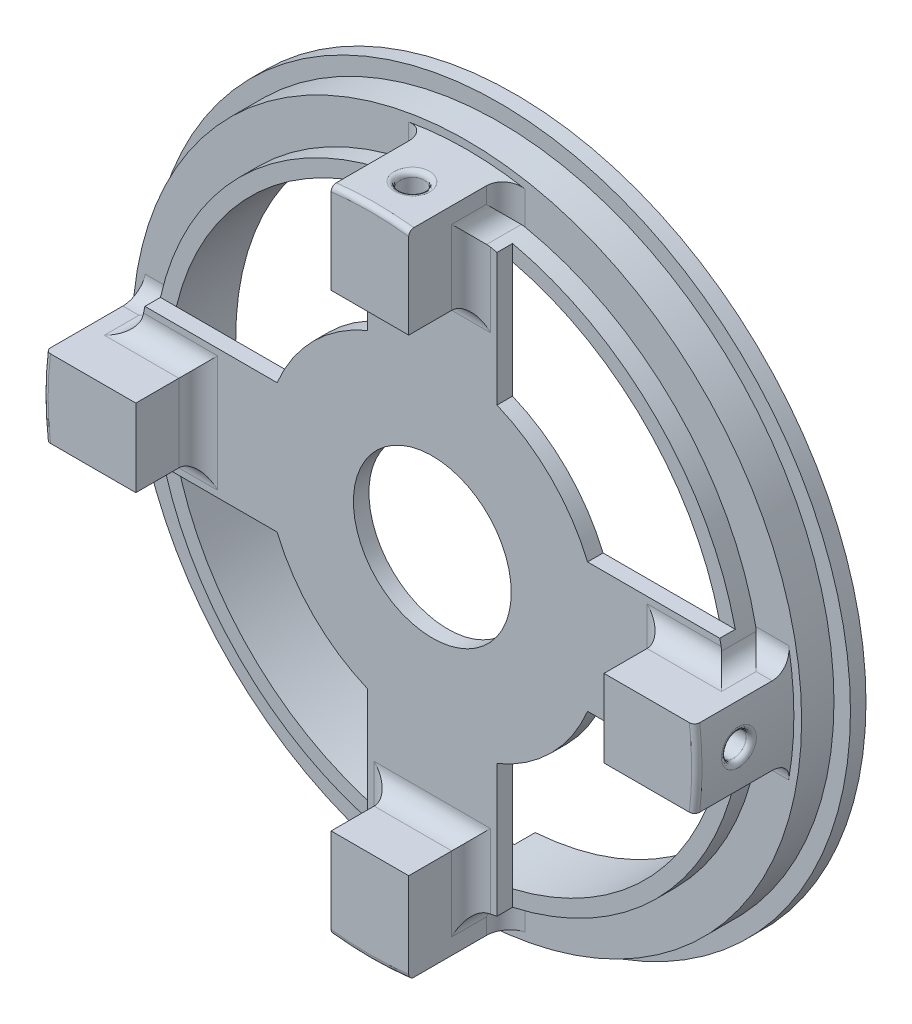
SolidWorks part; units mm, degrees
ref_plane "Front Plane" through (0, 0, 0) normal (0, 0, 1) x (1, 0, 0)
ref_plane "Top Plane" through (0, 0, 0) normal (0, 1, 0) x (1, 0, 0)
ref_plane "Right Plane" through (0, 0, 0) normal (1, 0, 0) x (0, 0, -1)
sketch "Sketch1" plane through (0, 0, 0) normal (0, 0, 1) x (1, 0, 0)
  circle A0 centre (0, 0) radius 54.3 construction
  circle A1 centre (0, 0) radius 54.3
  circle A4 centre (0, 0) radius 43.15
  circle A5 centre (0, 0) radius 43.15
extrude "Boss-Extrude1" add sketch "Sketch1" along normal blind 2.4
sketch "Sketch6" plane through (0, 0, 10.2) normal (0, 0, 1) x (1, 0, 0)
  circle A2 centre (0, 0) radius 43.15 construction
  circle A3 centre (0, 0) radius 43.15
extrude "Boss-Extrude4" add sketch "Sketch6" along normal blind 2.4 from offset 0.15 separate body
sketch "Sketch7" plane through (0, 0, 2.4) normal (0, 0, 1) x (1, 0, 0)
  circle A0 centre (0, 0) radius 43.15 construction
  circle A1 centre (0, 0) radius 43.15
extrude "Extrude-Thin2" add sketch "Sketch7" along normal up to surface (10.35 mm away) thin up to face at (43.15, 0, 12.75) thin type one direction wall 2.4
sketch "Sketch9" plane through (0, 0, 12.75) normal (0, 0, 1) x (1, 0, 0)
  circle A2 centre (0, 0) radius 12.2
  circle A3 centre (0, 0) radius 12.2
  dimension "D1" = 0.2
extrude "Cut-Extrude1" cut sketch "Sketch9" against normal up to surface (2.4 mm away) up to face at (43.15, 0, 10.35)
sketch "Sketch10" plane through (0, 0, 12.75) normal (0, 0, 1) x (1, 0, 0)
  line L0 (0, -45.55) -> (0, 45.55) construction
  line L1 (45.55, 0) -> (-45.55, 0) construction
  line L2 (10, -44.4387) -> (10, 44.4387)
  line L3 (44.4387, -10) -> (-44.4387, -10)
  line L4 (44.4387, 10) -> (-44.4387, 10)
  line L5 (-10, -44.4387) -> (-10, 44.4387)
  circle A0 centre (0, 0) radius 45.55 construction
  circle A1 centre (0, 0) radius 45.55
  circle A2 centre (0, 0) radius 26
  point P9 (10, 0)
  point P12 (0, -10)
  circle M7 centre (0, 0) radius 45.55
  dimension "D3" = 52
  dimension "D1" = 10
  dimension "D2" = 10
extrude "Cut-Extrude2" cut sketch "Sketch10" against normal up to surface (2.4 mm away) contours A2 L2 L3 M7 | A2 L3 L5 M7 | A2 L5 L4 M7 | A2 L4 L2 M7 region at (25.148, -25.148, 12.75) region at (-25.148, -25.148, 12.75) region at (-25.148, 25.148, 12.75) region at (25.148, 25.148, 12.75) up to face at (12.2, 0, 10.35)
sketch "Sketch8" plane through (0, 0, 2.4) normal (0, 0, 1) x (1, 0, 0)
  circle A2 centre (0, 0) radius 45.55 construction
  circle A3 centre (0, 0) radius 45.55
  circle A6 centre (0, 0) radius 51.75
  circle A7 centre (0, 0) radius 51.75
  dimension "D1" = 2.55
extrude "Boss-Extrude5" add sketch "Sketch8" along normal blind 5
sketch "Sketch12" plane through (0, 0, 7.4) normal (0, 0, 1) x (1, 0, 0)
  line L0 (0, 0) -> (-50.55, 0) construction
  line L1 (-50.1927, -6) -> (-36.1927, -6)
  line L2 (-36.1927, -6) -> (-36.1927, 6)
  line L3 (-50.1927, 6) -> (-36.1927, 6)
  circle A2 centre (0, 0) radius 50.55
  circle A3 centre (0, 0) radius 50.55
  point P8 (-36.1927, 0)
  circle M6 centre (0, 0) radius 45.55
  dimension "D2" = 6
  dimension "D3" = 14
  dimension "D1" = 1.2
extrude "Boss-Extrude6" add sketch "Sketch12" along normal blind 15 contours L2 L0 L1 M6 | L0 L2 L3 M6 | L0 A3 L1 M6 | L0 L3 A3 M6 region at (-40.8061, -2.9785, 7.4) region at (-40.8061, 2.9785, 7.4) region at (-47.9242, -3.0039, 7.4) region at (-47.9242, 3.0039, 7.4)
sketch "Sketch14" plane through (0, 0, 7.4) normal (0, 0, -1) x (-1, 0, 0)
  line L3 (42.7308, 6) -> (36.1927, 6)
  line L4 (36.1927, 6) -> (36.1927, -6)
  line L5 (36.1927, -6) -> (42.7308, -6)
  line L6 (42.7308, 6) -> (36.1927, 6)
  line L7 (36.1927, 6) -> (36.1927, -6)
  line L8 (36.1927, -6) -> (42.7308, -6)
  arc A1 (42.7308, -6) -> (42.7308, 6) centre (0, 0) ccw
  arc A2 (42.7308, -6) -> (42.7308, 6) centre (0, 0) ccw
  dimension "D1" = 0
extrude "Cut-Extrude4" cut sketch "Sketch14" against normal up to surface (2.95 mm away) up to face at (-7.8383, 0, 10.35)
sketch "Sketch13" plane through (-36.1927, 0, 0) normal (1, 0, 0) x (0, 0, -1)
  line L0 (-22.4, -6) -> (-22.4, 6) construction
  circle A0 centre (-15.9, 0) radius 1.9
  point P2 (-22.4, 0)
  dimension "D1" = 3.8
  dimension "D2" = 6.5
extrude "Cut-Extrude3" cut sketch "Sketch13" against normal through all from offset 5 offset against normal yes
fillet "Fillet1" radius 3 7 edges at (-36.1927, 0, 12.75) (-40.6729, -6, 12.75) (-45.1531, -6, 10.075) (-45.1531, 6, 10.075) (-40.6729, 6, 12.75) (-47.6729, -6, 7.4) (-47.6729, 6, 7.4)
fillet "Fillet2" radius 0.8 2 edges at (-50.55, 0, 22.4) (-50.5481, -0.4355, 17.7494)
pattern_circular "CirPattern4" count 4 over 360 about axis through (0, 0, 141.5849) along (0, 0, -1) of "Boss-Extrude6", "Cut-Extrude4", "Cut-Extrude3", "Fillet1", "Fillet2"
sketch "Sketch17" plane through (0, 0, 0) normal (0, 0, -1) x (-1, 0, 0)
  circle A0 centre (0, 0) radius 43.15 construction
  circle A1 centre (0, 0) radius 43.15
  ellipse E0 centre (0, 43) end of major axis (0, 39.2) minor radius 3 (2.9989, 42.8953) -> (-2.9989, 42.8953) ccw construction
  ellipse E1 centre (0, -43) end of major axis (0, -39.2) minor radius 3 (-2.9989, -42.8953) -> (2.9989, -42.8953) ccw construction
  ellipse E2 centre (0, 43) end of major axis (0, 39.2) minor radius 3 (2.9989, 42.8953) -> (-2.9989, 42.8953) ccw
  ellipse E3 centre (0, -43) end of major axis (0, -39.2) minor radius 3 (-2.9989, -42.8953) -> (2.9989, -42.8953) ccw
  spline S0 degree 1 poles (-3.1488, -42.892) (3.1488, -42.892) knots 0 0 1 1 construction
  spline S1 degree 3 poles (-3.1488, -42.892) (-3.1601, -43.4079) (-3.0156, -44.4646) (-2.1068, -46.2652) (0, -47.4065) (2.1068, -46.2652) (3.0156, -44.4646) (3.1601, -43.4079) (3.1488, -42.892) knots 1.54324 1.54324 1.54324 1.54324 1.942828 2.342417 3.141593 3.940769 4.340357 4.739945 4.739945 4.739945 4.739945
  spline S2 degree 1 poles (3.1488, 42.892) (-3.1488, 42.892) knots 0 0 1 1 construction
  spline S3 degree 3 poles (3.1488, 42.892) (3.1601, 43.4079) (3.0156, 44.4646) (2.1068, 46.2652) (0, 47.4065) (-2.1068, 46.2652) (-3.0156, 44.4646) (-3.1601, 43.4079) (-3.1488, 42.892) knots 1.54324 1.54324 1.54324 1.54324 1.942828 2.342417 3.141593 3.940769 4.340357 4.739945 4.739945 4.739945 4.739945
  circle M3 centre (0, 0) radius 43.15
extrude "Cut-Extrude5" cut sketch "Sketch17" against normal blind 3.2 contours E2 M3 | A1 S3 E2 | E3 M3 | A1 S1 E3 M3 region at (-3.0801, 43.1143, 0) region at (0, -46.8758, 0) region at (0, 44.6747, 0) region at (0, -44.6747, 0)
equation "\"D1@Boss-Extrude1\"=\"Wall thickness@BOX_PLAYERS.Assembly\""
equation "\"D1@Sketch1\"=\"Gap@BOX_PLAYERS.Assembly\""
equation "\"D1@Boss-Extrude4\"=\"Wall thickness@BOX_PLAYERS.Assembly\""
equation "\"D19@Boss-Extrude4\"=\"Gap@BOX_PLAYERS.Assembly\""
equation "\"D5@Extrude-Thin2\"=\"Wall thickness@BOX_PLAYERS.Assembly\""
equation "\"D1@Sketch8\"=\"Wall thickness@BOX_PLAYERS.Assembly\"+\"Gap@BOX_PLAYERS.Assembly\""
equation "\"D1@Sketch12\"=\"Body thickening@BOX_PLAYERS.Assembly\""
equation "\"D1@Sketch13\"=\"Sleeve@BOX_PLAYERS.Assembly\""
equation "\"D1@Sketch17\"=\"Gap@BOX_PLAYERS.Assembly\""
